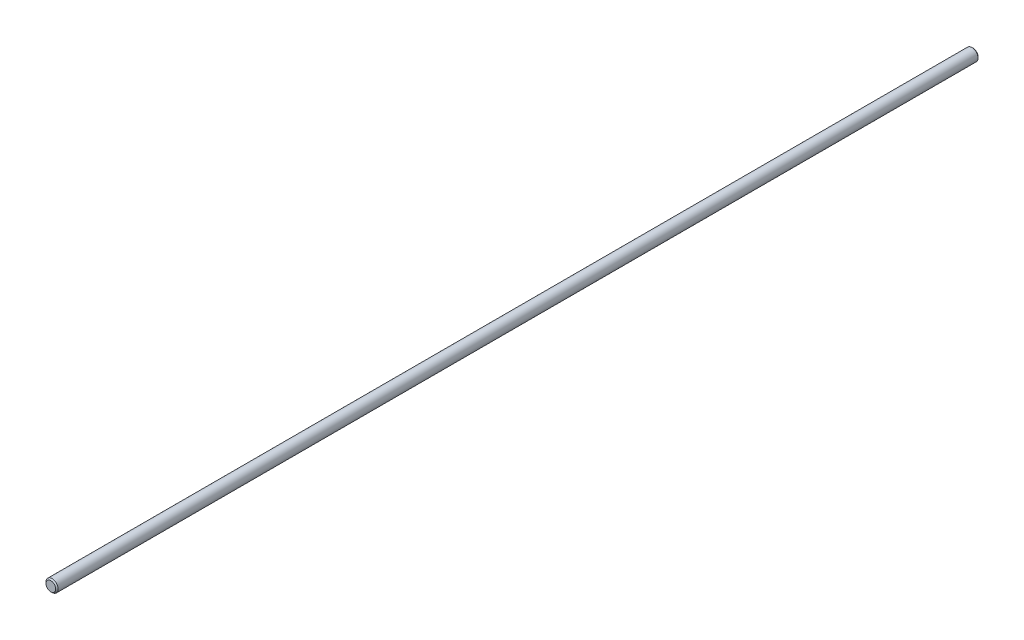
SolidWorks part; units mm, degrees
material "AISI 303 Stainless"
ref_plane "Front" through (0, 0, 0) normal (0, 0, 1) x (1, 0, 0)
ref_plane "Top" through (0, 0, 0) normal (0, 1, 0) x (1, 0, 0)
ref_plane "Right" through (0, 0, 0) normal (1, 0, 0) x (0, 0, -1)
sketch "Sketch1" plane through (0, 0, 0) normal (0, 0, 1) x (1, 0, 0)
  circle A0 centre (0, 0) radius 3.175
  dimension "dia" = 6.35
sketch "Sketch3" plane through (0, 0, 0) normal (0, 0, 1) x (1, 0, 0)
  circle A0 centre (0, 0) radius 3.175 construction
  circle A1 centre (0, 0) radius 3.175
extrude "Boss-Extrude1" add sketch "Sketch3" along normal mid plane 482.6
sketch "Sketch2" plane through (0, 0, 0) normal (1, 0, 0) x (0, 0, -1)
  line L0 (241.3, 3.175) -> (-241.3, 3.175) construction
  point P0 (-241.3, 3.175)
  point P1 (241.3, 3.175)
  point P2 (-228.6, 3.175)
  point P3 (228.6, 3.175)
  dimension "D1" = 12.7
  dimension "D2" = 12.7
chamfer "Chamfer1" distance 0.635 angle 45 2 edges at (3.175, 0, 241.3) (3.175, 0, -241.3)
ref_axis "Axis1" through (0, 0, -265.43) along (0, 0, 1)
equation "\"D1@Chamfer1\" = \"dia@Sketch1\" / 10"
equation "\"D1@Sketch2\"= \"dia@Sketch1\" * 2"
equation "\"D2@Sketch2\"=\"D1@Sketch2\""
